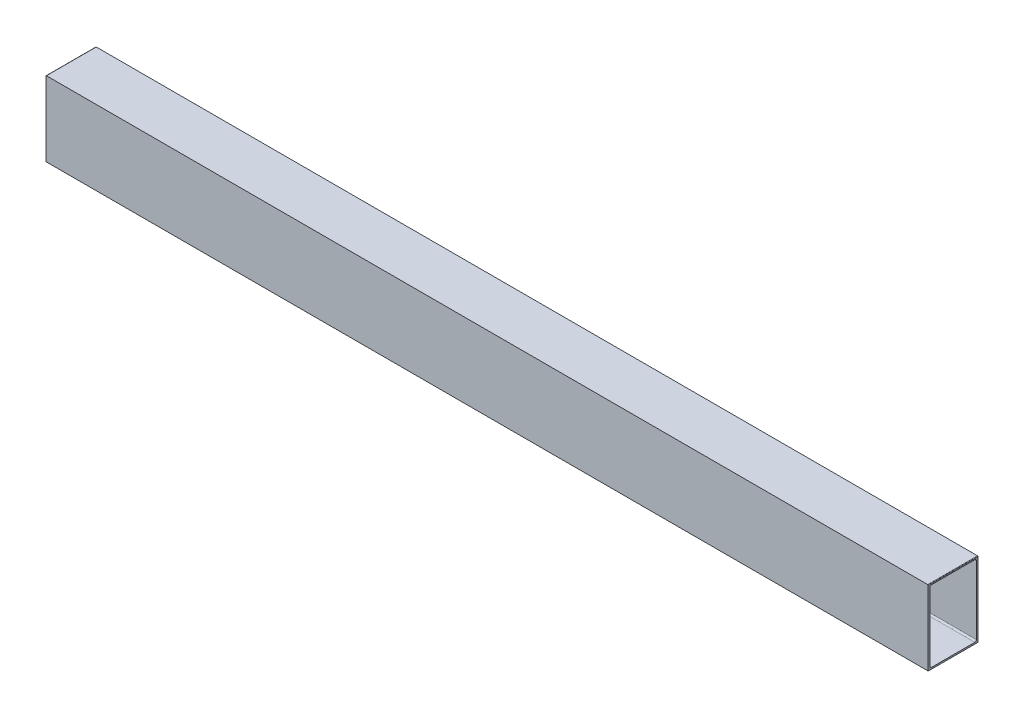
SolidWorks part; units mm, degrees
material "ASTM A500 Grade B Steel"
ref_plane "Front Plane" through (0, 0, 0) normal (0, 0, 1) x (1, 0, 0)
ref_plane "Top Plane" through (0, 0, 0) normal (0, 1, 0) x (1, 0, 0)
ref_plane "Right Plane" through (0, 0, 0) normal (1, 0, 0) x (0, 0, -1)
sketch "Sketch1" plane through (0, 0, 0) normal (1, 0, 0) x (0, 0, -1)
  line L0 (-98.425, 6.35) -> (-98.425, 146.05)
  line L1 (0, 0) -> (-101.6, 0)
  line L2 (0, 0) -> (0, 152.4)
  line L3 (0, 152.4) -> (-101.6, 152.4)
  line L4 (-101.6, 0) -> (-101.6, 152.4)
  line L5 (-6.35, 149.225) -> (-95.25, 149.225)
  line L6 (-3.175, 6.35) -> (-3.175, 146.05)
  line L7 (-6.35, 3.175) -> (-95.25, 3.175)
  line L8 (-98.425, 3.175) -> (-98.425, 149.225) construction
  line L9 (-3.175, 3.175) -> (-98.425, 3.175) construction
  line L10 (-3.175, 3.175) -> (-3.175, 149.225) construction
  line L11 (-3.175, 149.225) -> (-98.425, 149.225) construction
  arc A0 (-98.425, 6.35) -> (-95.25, 3.175) centre (-95.25, 6.35) ccw
  arc A1 (-3.175, 6.35) -> (-6.35, 3.175) centre (-6.35, 6.35) cw
  arc A2 (-6.35, 149.225) -> (-3.175, 146.05) centre (-6.35, 146.05) cw
  arc A3 (-98.425, 146.05) -> (-95.25, 149.225) centre (-95.25, 146.05) cw
  dimension "D4" = 3.175
  dimension "D1" = 152.4
  dimension "D2" = 101.6
  dimension "D3" = 3.175
extrude "Boss-Extrude1" add sketch "Sketch1" along normal blind 1800
fillet "Fillet1" radius 1 1 edges at (0, 152.4, 50.8)
fillet "Fillet2" radius 1 1 edges at (1800, 152.4, 50.8)
equation "\"D4@Sketch1\"=\"D3@Sketch1\""
